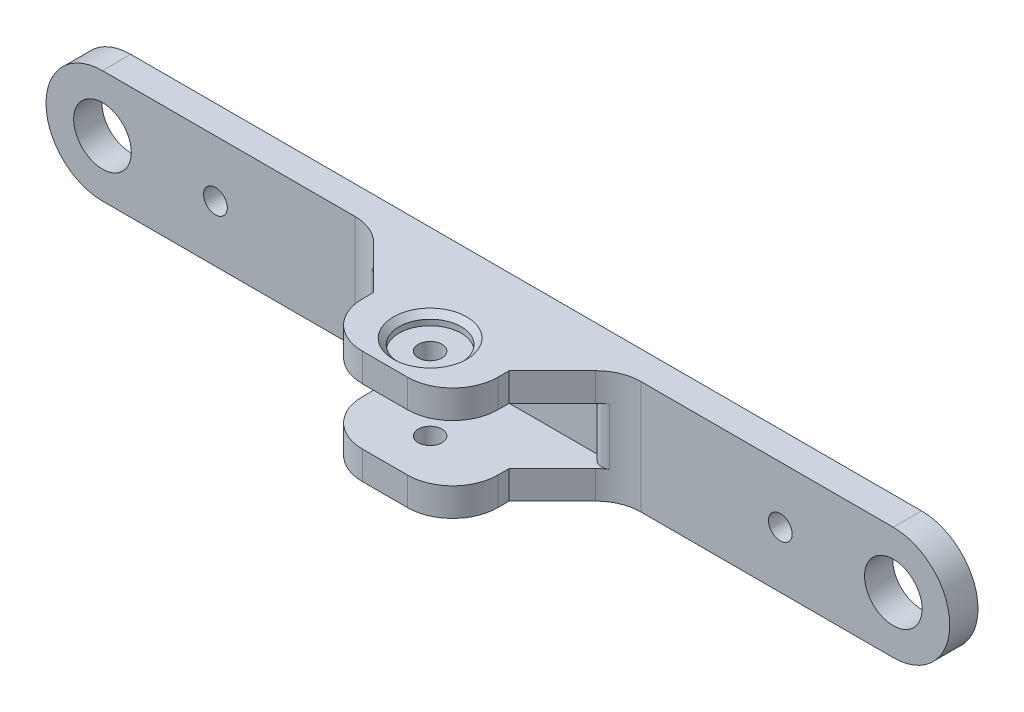
SolidWorks part; units mm, degrees
ref_plane "Plan de face" through (0, 0, 0) normal (0, 0, 1) x (1, 0, 0)
ref_plane "Plan de dessus" through (0, 0, 0) normal (0, 1, 0) x (1, 0, 0)
ref_plane "Plan de droite" through (0, 0, 0) normal (1, 0, 0) x (0, 0, -1)
sketch "Esquisse1" plane through (0, 0, 0) normal (0, 0, 1) x (1, 0, 0)
  line L0 (-70, 0) -> (70, 0) construction
  line L1 (-70, 10) -> (70, 10)
  line L2 (-70, -10) -> (70, -10)
  arc A0 (-70, 10) -> (-70, -10) centre (-70, 0) ccw
  arc A1 (70, -10) -> (70, 10) centre (70, 0) ccw
  point P3 (0, 0)
  dimension "D1" = 140
  dimension "D2" = 20
  dimension "D3" = 70
extrude "Boss.-Extru.1" add sketch "Esquisse1" along normal blind 5
sketch "Esquisse2" plane through (0, 0, 5) normal (0, 0, 1) x (1, 0, 0)
  line L0 (70, 10) -> (-70, 10) construction
  circle A0 centre (-70, 0) radius 5.1
  circle A1 centre (70, 0) radius 5.1
  arc A2 (-70, 10) -> (-70, -10) centre (-70, 0) ccw construction
  arc A3 (70, -10) -> (70, 10) centre (70, 0) ccw construction
  circle A4 centre (-50, 0) radius 2.1
  circle A5 centre (50, 0) radius 2.1
  dimension "D1" = 10.2
  dimension "D2" = 10.2
  dimension "D3" = 4.2
  dimension "D4" = 4.2
  dimension "D5" = 100
  dimension "D6" = 50
  dimension "D7" = 10
  dimension "D8" = 10
extrude "Enlèv. mat.-Extru.1" cut sketch "Esquisse2" against normal through all
sketch "Esquisse3" plane through (0, 0, 5) normal (0, 0, 1) x (1, 0, 0)
  line L0 (70, 10) -> (-70, 10) construction
  line L1 (-12, 10) -> (12, 10)
  line L2 (-12, 10) -> (-12, -10)
  line L3 (-12, -10) -> (12, -10)
  line L4 (12, 10) -> (12, -10)
  line L5 (-70, -10) -> (70, -10) construction
  dimension "D1" = 24
  dimension "D2" = 12
extrude "Boss.-Extru.2" add sketch "Esquisse3" along normal blind 20
chamfer "Chanfrein1" distance 10 angle 45 2 edges
sketch "Esquisse4" plane through (0, 0, 25) normal (0, 0, 1) x (1, 0, 0)
  line L0 (12, 10) -> (-12, 10) construction
  line L1 (-18, 5) -> (18, 5)
  line L2 (-18, 5) -> (-18, -5)
  line L3 (-18, -5) -> (18, -5)
  line L4 (18, 5) -> (18, -5)
  line L5 (-12, 10) -> (-12, -10) construction
  line L6 (12, -10) -> (12, 10) construction
  dimension "D1" = 10
  dimension "D2" = 5
  dimension "D3" = 6
  dimension "D4" = 6
extrude "Enlèv. mat.-Extru.2" cut sketch "Esquisse4" against normal blind 20
sketch "Esquisse5" plane through (0, 10, 0) normal (0, 1, 0) x (1, 0, 0)
  line L0 (12, -25) -> (-12, -25) construction
  line L1 (-12, -25) -> (-12, -15) construction
  circle A0 centre (0, -17) radius 2.1
  dimension "D1" = 4.2
  dimension "D2" = 8
  dimension "D3" = 12
extrude "Enlèv. mat.-Extru.3" cut sketch "Esquisse5" against normal through all
fillet "Congé1" radius 8 6 edges at (-22, 0, 5) (-12, -7.5, 25) (12, -7.5, 25) (22, 0, 5) (-12, 7.5, 25) (12, 7.5, 25)
sketch "Esquisse6" plane through (0, 10, 0) normal (0, 1, 0) x (1, 0, 0)
  circle A0 centre (0, -17) radius 5.5
  dimension "D1" = 11
extrude "Enlèv. mat.-Extru.4" cut sketch "Esquisse6" against normal blind 2
chamfer "Chanfrein2" distance 1 angle 45 1 edges at (0, 10, 22.5)
fillet "Congé4" radius 2 2 edges at (18, 0, 9) (-18, 0, 9)
